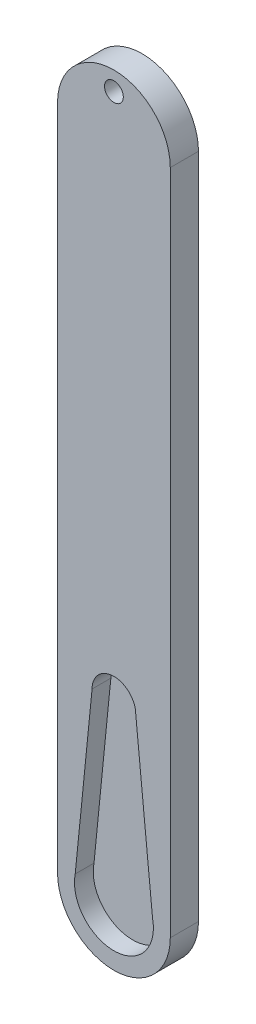
SolidWorks part; units mm, degrees
ref_plane "Front Plane" through (0, 0, 0) normal (0, 0, 1) x (1, 0, 0)
ref_plane "Top Plane" through (0, 0, 0) normal (0, 1, 0) x (1, 0, 0)
ref_plane "Right Plane" through (0, 0, 0) normal (1, 0, 0) x (0, 0, -1)
sketch "Sketch1" plane through (0, 0, 0) normal (0, 0, 1) x (1, 0, 0)
  line L0 (0, 6) -> (0, 0)
  line L1 (0, 0) -> (12, 0)
  line L2 (0, 0) -> (0, 83)
  line L3 (0, 83) -> (12, 83)
  line L4 (12, 0) -> (12, 83)
  line L5 (6, 0) -> (12, 0)
  line L6 (12, 0) -> (12, 6)
  line L7 (6, 6) -> (6, 27.1) construction
  line L8 (3.675, 24.775) -> (1.8829, 6.8306)
  line L9 (8.325, 24.775) -> (10.1171, 6.8306)
  arc A0 (0, 6) -> (12, 6) centre (6, 6) ccw
  arc A1 (1.8829, 6.8306) -> (10.1171, 6.8306) centre (6, 6) ccw
  arc A2 (8.325, 24.775) -> (3.675, 24.775) centre (6, 24.775) ccw
  dimension "D3" = 12
  dimension "D4" = 8.4
  dimension "D6" = 4.65
  dimension "D1" = 12
  dimension "D2" = 83
  dimension "D5" = 21.1
extrude "Boss-Extrude1" add sketch "Sketch1" along normal blind 3 contours L2 A0 L4 L3 A2 L9 A1 L8 region at (6, 47.7023, 0)
extrude "Boss-Extrude2" add sketch "Sketch1<3>" along normal blind 1 contours L9 A2 L8 A1 region at (6, 13.2973, 0)
sketch "Sketch1<3>" plane through (0, 0, 0) normal (0, 0, 1) x (1, 0, 0) same geometry as "Sketch1"
sketch "Sketch2" plane through (0, 0, 3) normal (0, 0, 1) x (1, 0, 0)
  line L0 (0, 83) -> (12, 83) construction
  line L1 (12, 6) -> (12, 83) construction
  line L2 (0, 77) -> (0, 83)
  line L3 (0, 83) -> (6, 83)
  line L4 (6, 83) -> (12, 83)
  line L5 (12, 83) -> (12, 77)
  arc A0 (12, 77) -> (0, 77) centre (6, 77) ccw
  circle A1 centre (6, 81) radius 1
  line M7 (0, 83) -> (0, 6)
  line M9 (12, 6) -> (12, 83)
  line M10 (12, 83) -> (0, 83)
  dimension "D1" = 12
  dimension "D3" = 2
  dimension "D2" = 2
extrude "Cut-Extrude1" cut sketch "Sketch2" against normal through all contours A0 M10 M7 | A0 M9 M10 | A1 region at (10.6598, 81.6598, 3) region at (1.3402, 81.6598, 3) region at (6, 81, 3)
